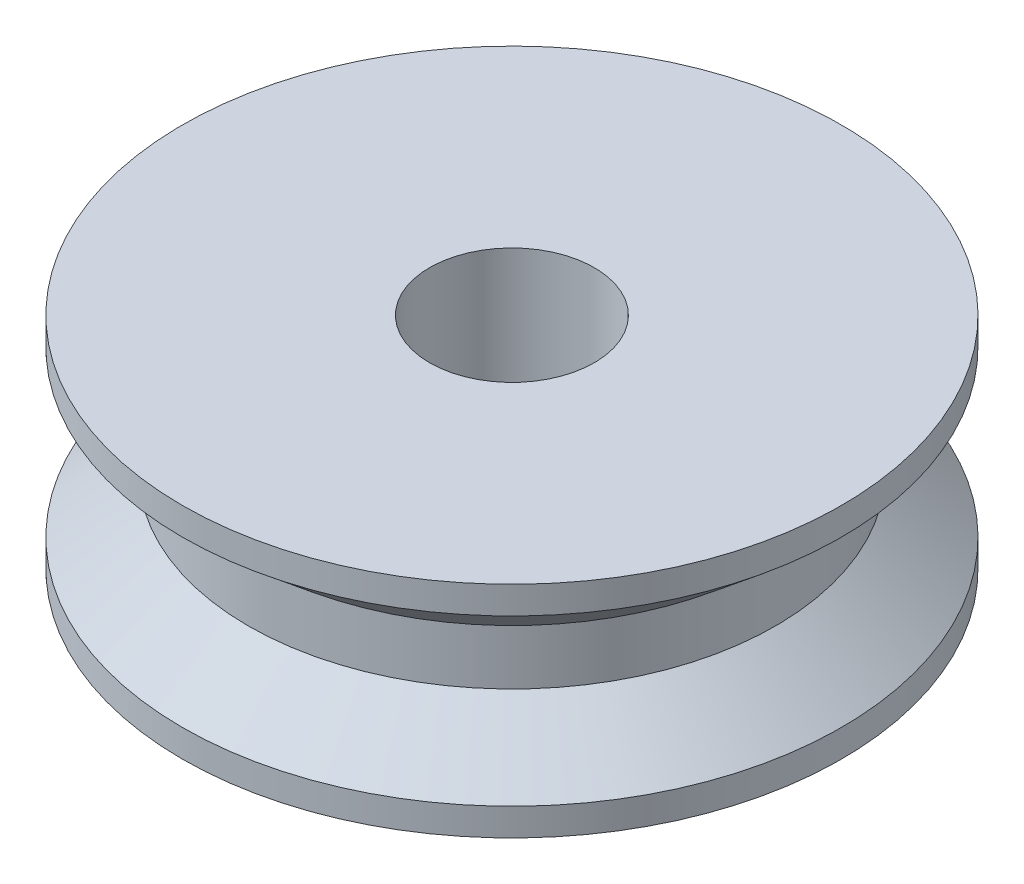
SolidWorks part; units mm, degrees
ref_plane "Front Plane" through (0, 0, 0) normal (0, 0, 1) x (1, 0, 0)
ref_plane "Top Plane" through (0, 0, 0) normal (0, 1, 0) x (1, 0, 0)
ref_plane "Right Plane" through (0, 0, 0) normal (1, 0, 0) x (0, 0, -1)
sketch "Sketch1" plane through (0, 0, 0) normal (0, 1, 0) x (1, 0, 0)
  circle A0 centre (0, 0) radius 6
  circle A1 centre (0, 0) radius 1.5
extrude "Boss-Extrude1" add sketch "Sketch1" along normal blind 4
sketch "Sketch6" plane through (0, 0, 0) normal (0, 0, 1) x (1, 0, 0)
  line L4 (6, 0.5) -> (6, 3.5)
  line L6 (4.8, 2.5) -> (4.8, 1.5)
  line L7 (4.8, 2.5) -> (6, 3.5)
  line L8 (4.8, 1.5) -> (6, 0.5)
revolve "Cut-Revolve1" cut sketch "Sketch6" angle 360 about axis through (0, 4, 0) along (0, -1, 0)
